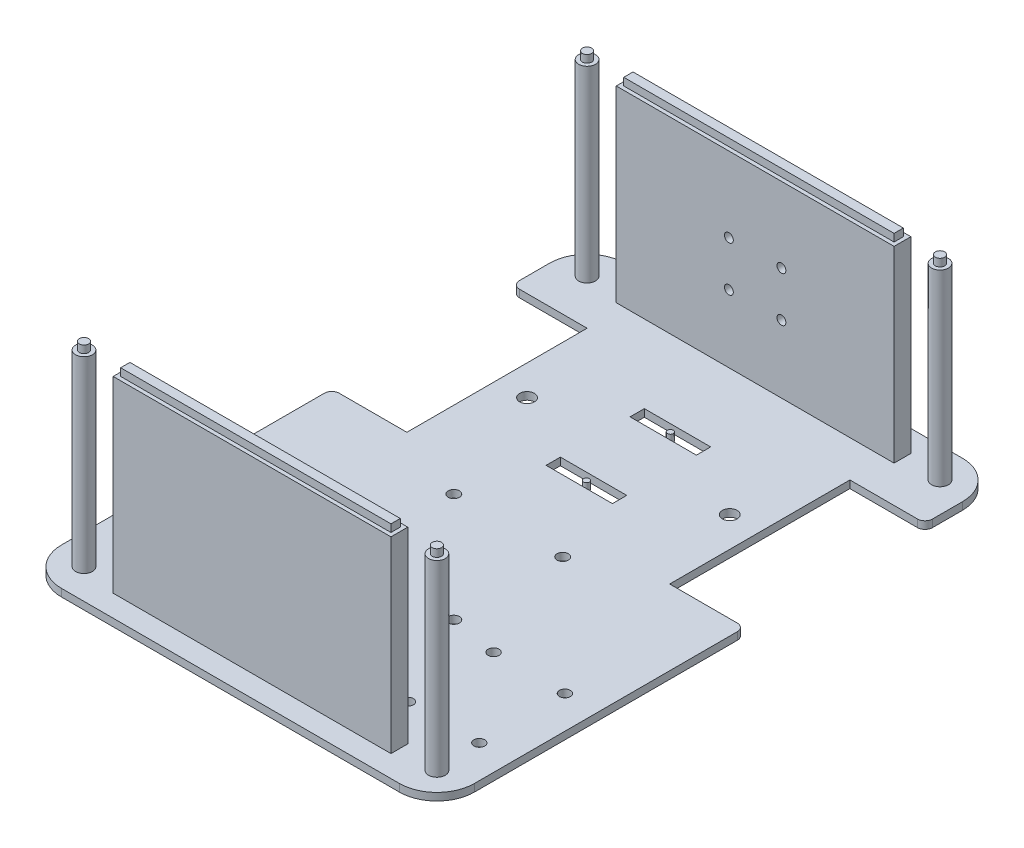
SolidWorks part; units mm, degrees
material "ABS"
ref_plane "Front Plane" through (0, 0, 0) normal (0, 0, 1) x (1, 0, 0)
ref_plane "Top Plane" through (0, 0, 0) normal (0, 1, 0) x (1, 0, 0)
ref_plane "Right Plane" through (0, 0, 0) normal (1, 0, 0) x (0, 0, -1)
sketch "Sketch2" plane through (0, 0, 0) normal (0, 1, 0) x (1, 0, 0)
  line L0 (-148.7583, 0) -> (98.0966, 0) construction
  line L1 (-69.85, -95.25) -> (69.85, -95.25)
  line L2 (-69.85, -95.25) -> (-69.85, 95.25)
  line L3 (-69.85, 95.25) -> (69.85, 95.25)
  line L4 (69.85, -95.25) -> (69.85, 95.25)
  line L5 (-69.85, -95.25) -> (69.85, 95.25) construction
  line L6 (-69.85, 95.25) -> (69.85, -95.25) construction
  line L7 (0, 121.1686) -> (0, -125.6862) construction
  point P0 (0, 0)
  dimension "D1" = 190.5
  dimension "D2" = 139.7
extrude "Base Plate" add sketch "Sketch2" along normal blind 2.54
sketch "Sketch4" plane through (0, 2.54, 0) normal (0, 1, 0) x (1, 0, 0)
  line L0 (0, -95.25) -> (0, 95.25) construction
  line L1 (-69.85, -95.25) -> (69.85, -95.25) construction
  line L2 (69.85, 95.25) -> (-69.85, 95.25) construction
  line L3 (-34.66, -69.85) -> (-34.66, -40.894) construction
  line L4 (-34.66, -40.894) -> (-58.79, -40.894) construction
  line L5 (-58.79, -40.894) -> (-58.79, -69.85) construction
  line L6 (-58.79, -69.85) -> (-34.66, -69.85) construction
  line L7 (69.85, -95.25) -> (69.85, 95.25) construction
  line L8 (-69.85, 95.25) -> (-69.85, -95.25) construction
  circle A0 centre (-58.79, -69.85) radius 1.8415
  circle A1 centre (-34.66, -69.85) radius 1.8415
  circle A2 centre (-34.66, -40.894) radius 1.8415
  circle A3 centre (-58.79, -40.894) radius 1.8415
  circle A4 centre (34.66, -69.85) radius 1.8415
  circle A5 centre (58.79, -69.85) radius 1.8415
  circle A6 centre (58.79, -40.894) radius 1.8415
  circle A7 centre (34.66, -40.894) radius 1.8415
  point P0 (-58.79, -69.85)
  point P1 (-58.79, -40.894)
  point P2 (-34.66, -40.894)
  point P3 (-34.66, -69.85)
  dimension "D4" = 3.683
  dimension "D1" = 28.956
  dimension "D2" = 24.13
  dimension "D3" = 11.06
  dimension "D5" = 25.4
extrude "L-Bracket holes" cut sketch "Sketch4" against normal blind 6.35
sketch "Sketch5" plane through (0, 2.54, 0) normal (0, 1, 0) x (1, 0, 0)
  line L0 (-69.85, 8.89) -> (-44.45, 8.89)
  line L1 (-69.85, 95.25) -> (-69.85, -95.25) construction
  line L2 (-44.45, 8.89) -> (-44.45, 69.85)
  line L3 (-44.45, 69.85) -> (-69.85, 69.85)
  line L4 (-69.85, 69.85) -> (-69.85, 8.89)
  line L5 (-69.85, -95.25) -> (69.85, -95.25) construction
  line L6 (69.85, 95.25) -> (-69.85, 95.25) construction
  line L7 (0, -95.25) -> (0, 95.25) construction
  line L8 (-58.79, -40.894) -> (-34.66, -40.894) construction
  line L9 (44.45, 69.85) -> (69.85, 69.85)
  line L10 (44.45, 8.89) -> (44.45, 69.85)
  line L11 (69.85, 8.89) -> (44.45, 8.89)
  line L12 (69.85, 69.85) -> (69.85, 8.89)
  dimension "D1" = 25.4
  dimension "D2" = 60.96
  dimension "D3" = 25.4
extrude "Steering Wheels Holes" cut sketch "Sketch5" against normal blind 6.35
fillet "Fillet1" radius 12.7 4 edges at (69.85, 1.27, -95.25) (-69.85, 1.27, -95.25) (69.85, 1.27, 95.25) (-69.85, 1.27, 95.25)
fillet "Fillet2" radius 2.54 4 edges at (69.85, 1.27, -69.85) (69.85, 1.27, -8.89) (-69.85, 1.27, -8.89) (-69.85, 1.27, -69.85)
sketch "Sketch6" plane through (0, 2.54, 0) normal (0, 1, 0) x (1, 0, 0)
  line L0 (-69.85, -95.25) -> (-69.85, 95.25) construction
  line L1 (-69.85, -95.25) -> (69.85, -95.25) construction
  line L2 (0, -88.935) -> (0, 95.5267) construction
  line L3 (-69.85, 6.35) -> (69.85, 6.35) construction
  point P0 (-59.69, -85.09)
  point P12 (-59.69, 97.79)
  point P13 (59.69, -85.09)
  point P14 (59.69, 97.79)
  dimension "D1" = 10.16
  dimension "D2" = 10.16
sketch "Sketch13" plane through (0, 2.54, 0) normal (0, 1, 0) x (1, 0, 0)
  line L0 (-69.85, -38.1) -> (69.85, -38.1) construction
  line L2 (-69.85, 6.35) -> (-69.85, -82.55) construction
  line L3 (69.85, -82.55) -> (69.85, 6.35) construction
  line L5 (-34.66, -69.85) -> (-34.66, -40.894) construction
  line L6 (34.66, -69.85) -> (34.66, -40.894) construction
  line L7 (-18.415, -38.1) -> (18.415, -38.1) construction
  line L8 (18.415, -38.1) -> (18.415, -1.27) construction
  line L9 (18.415, -1.27) -> (-18.415, -1.27) construction
  line L10 (-18.415, -1.27) -> (-18.415, -38.1) construction
  circle A0 centre (-18.415, -1.27) radius 1.905
  circle A1 centre (-18.415, -38.1) radius 1.905
  circle A2 centre (18.415, -38.1) radius 1.905
  circle A3 centre (18.415, -1.27) radius 1.905
  dimension "D1" = 3.81
  dimension "D4" = 36.83
  dimension "D5" = 36.83
extrude "Holes for L298" cut sketch "Sketch13" against normal blind 6.35
sketch "Sketch14" plane through (0, 2.54, 0) normal (0, 1, 0) x (1, 0, 0)
  line L0 (11.2203, 51.155) -> (-11.2203, 51.155)
  line L1 (11.2203, 22.755) -> (-11.2203, 22.755)
  line L2 (11.2203, 22.755) -> (11.2203, 27.585)
  line L3 (11.2203, 27.585) -> (-11.2203, 27.585)
  line L4 (0, 95.25) -> (0, -56.8347) construction
  line L5 (57.15, 95.25) -> (-57.15, 95.25) construction
  line L6 (-11.2203, 22.755) -> (-11.2203, 27.585)
  line L7 (-44.45, 39.37) -> (44.45, 39.37) construction
  line L8 (-44.45, 8.89) -> (-44.45, 69.85) construction
  line L9 (44.45, 69.85) -> (44.45, 8.89) construction
  line L10 (11.2203, 22.755) -> (-11.2203, 27.585) construction
  line L11 (11.2203, 27.585) -> (-11.2203, 22.755) construction
  line L12 (-11.2203, 55.985) -> (-11.2203, 51.155)
  line L13 (11.2203, 55.985) -> (-11.2203, 55.985)
  line L14 (11.2203, 55.985) -> (11.2203, 51.155)
  circle A2 centre (0, 25.17) radius 0.9906
  circle A3 centre (0, 53.57) radius 0.9906
  dimension "D3" = 4.83
  dimension "D2" = 1.9812
  dimension "D1" = 14.2
extrude "Cut-Extrude4" cut sketch "Sketch14" against normal blind 6.35
sketch "Sketch15" plane through (0, 2.54, 0) normal (0, 1, 0) x (1, 0, 0)
  line L0 (-69.85, -95.25) -> (-69.85, 95.25) construction
  line L1 (-69.85, 95.25) -> (69.85, 95.25) construction
  line L2 (0, 95.25) -> (0, 49.0943) construction
  line L3 (0, 121.1686) -> (0, -125.6862) construction
  circle A0 centre (-59.69, 85.09) radius 1.57
  circle A1 centre (-59.69, 85.09) radius 2.84
  point P0 (-59.69, 85.09)
  point P5 (59.69, 85.09)
  dimension "D3" = 3.14
  dimension "D1" = 10.16
  dimension "D2" = 10.16
  dimension "D4" = 1.27
sketch "Sketch18" plane through (0, 2.54, 0) normal (0, 1, 0) x (1, 0, 0)
  line L0 (-44.45, 39.37) -> (44.45, 39.37) construction
  line L1 (-44.45, 8.89) -> (-44.45, 69.85) construction
  line L2 (44.45, 69.85) -> (44.45, 8.89) construction
  line L3 (0, 95.25) -> (0, -95.25) construction
  line L4 (57.15, 95.25) -> (-57.15, 95.25) construction
  line L5 (-57.15, -95.25) -> (57.15, -95.25) construction
  point P12 (-34.29, 39.37)
  point P13 (34.29, 39.37)
  dimension "D1" = 10.16
hole_wizard "holes for steering" positions "Sketch19" profile "Sketch20" tap size "M6x1.0" standard "ANSI Metric" end condition through all
sketch "Sketch19" plane through (0, 2.54, 0) normal (0, 1, 0) x (1, 0, 0)
  point P0 (-34.29, 39.37)
  point P3 (34.29, 39.37)
sketch "Sketch20" plane through (-34.29, 2.54, -39.37) normal (1, 0, 0) x (0, 0, 1)
  line L0 (0, 0) -> (0, 2.54)
  line L1 (0, 2.54) -> (2.5, 2.54)
  line L2 (2.5, 2.54) -> (2.5, 0)
  line L5 (2.5, 0) -> (0, 0)
  line L11 (0, -6.35) -> (0, 107.95) construction
  dimension "Thru Tap Drill Dia." = 5
  dimension "Thru Tap Drill Depth" = 2.54
cosmetic thread "Hole Thread11" parameters "D2"=6
cosmetic thread "Hole Thread12" parameters "D2"=6
extrude "Boss-Extrude3" add sketch "Sketch15" along normal blind 63.5
extrude "Boss-Extrude4" add sketch "Sketch15<2>" along normal blind 66.04 contours A0 region at (-59.69, 2.54, -85.09)
sketch "Sketch15<2>" plane through (0, 2.54, 0) normal (0, 1, 0) x (1, 0, 0) same geometry as "Sketch15"
mirror "Mirror1" about plane through (0, 0, 0) normal (1, 0, 0) of "Boss-Extrude4"
mirror "Mirror2" about plane through (0, 0, 0) normal (1, 0, 0) of "Boss-Extrude3"
sketch "Sketch23" plane through (0, 2.54, 0) normal (0, 1, 0) x (1, 0, 0)
  line L0 (0, 95.25) -> (0, -95.25) construction
  line L1 (-69.85, 6.35) -> (-69.85, -82.55) construction
  line L2 (-57.15, -95.25) -> (57.15, -95.25) construction
  circle A0 centre (-59.69, -85.09) radius 1.57
  circle A1 centre (-59.69, -85.09) radius 2.84
  dimension "D1" = 3.14
  dimension "D3" = 10.16
  dimension "D4" = 10.16
  dimension "D2" = 1.27
extrude "Boss-Extrude5" add sketch "Sketch23" along normal blind 63.5
extrude "Boss-Extrude6" add sketch "Sketch23<2>" along normal blind 66.04 contours A0 region at (-59.69, 2.54, 85.09)
sketch "Sketch23<2>" plane through (0, 2.54, 0) normal (0, 1, 0) x (1, 0, 0) same geometry as "Sketch23"
mirror "Mirror3" about plane through (0, 0, 0) normal (1, 0, 0) of "Boss-Extrude6", "Boss-Extrude5"
sketch "Sketch24" plane through (0, 2.54, 0) normal (0, 1, 0) x (1, 0, 0)
  line L0 (-59.69, -87.93) -> (59.69, -87.93) construction
  line L1 (-59.69, -82.25) -> (59.69, -82.25) construction
  line L2 (-59.69, 82.25) -> (59.69, 82.25) construction
  line L3 (-46.99, -87.93) -> (46.99, -87.93)
  line L4 (-46.99, -87.93) -> (-46.99, -82.25)
  line L5 (-46.99, -82.25) -> (46.99, -82.25)
  line L6 (46.99, -87.93) -> (46.99, -82.25)
  line L7 (59.69, 87.93) -> (-59.69, 87.93) construction
  line L9 (-46.99, 82.25) -> (46.99, 82.25)
  line L10 (-46.99, 82.25) -> (-46.99, 87.93)
  line L11 (-46.99, 87.93) -> (46.99, 87.93)
  line L12 (46.99, 82.25) -> (46.99, 87.93)
  circle A0 centre (-59.69, -85.09) radius 2.84 construction
  circle A1 centre (59.69, -85.09) radius 2.84 construction
  circle A2 centre (-59.69, -85.09) radius 2.84 construction
  circle A3 centre (-59.69, 85.09) radius 2.84 construction
  circle A4 centre (-59.69, 85.09) radius 2.84 construction
  circle A5 centre (59.69, 85.09) radius 2.84 construction
  circle A6 centre (59.69, 85.09) radius 2.84 construction
  dimension "D1" = 12.7
  dimension "D2" = 12.7
  dimension "D3" = 12.7
  dimension "D4" = 12.7
extrude "Boss-Extrude7" add sketch "Sketch24" along normal blind 63.5
sketch "Sketch25" plane through (0, 66.04, 0) normal (0, 1, 0) x (1, 0, 0)
  line L8 (-45.72, -83.52) -> (-45.72, -86.66)
  line L9 (-45.72, -86.66) -> (45.72, -86.66)
  line L10 (45.72, -86.66) -> (45.72, -83.52)
  line L11 (45.72, -83.52) -> (-45.72, -83.52)
  line L12 (-45.72, -83.52) -> (-45.72, -86.66)
  line L13 (-45.72, -86.66) -> (45.72, -86.66)
  line L14 (45.72, -86.66) -> (45.72, -83.52)
  line L15 (45.72, -83.52) -> (-45.72, -83.52)
  line L20 (-45.72, 86.66) -> (-45.72, 83.52)
  line L21 (-45.72, 83.52) -> (45.72, 83.52)
  line L22 (45.72, 83.52) -> (45.72, 86.66)
  line L23 (45.72, 86.66) -> (-45.72, 86.66)
  line L24 (-45.72, 86.66) -> (-45.72, 83.52)
  line L25 (-45.72, 83.52) -> (45.72, 83.52)
  line L26 (45.72, 83.52) -> (45.72, 86.66)
  line L27 (45.72, 86.66) -> (-45.72, 86.66)
  dimension "D1" = 1.27
  dimension "D2" = 1.27
extrude "Boss-Extrude8" add sketch "Sketch25" along normal blind 2.54
sketch "Sketch26" plane through (0, 0, -87.93) normal (0, 0, -1) x (-1, 0, 0)
  line L0 (0, 66.04) -> (0, 83.3576) construction
  line L1 (-46.99, 66.04) -> (46.99, 66.04) construction
  line L2 (-8.89, 40.64) -> (-8.89, -18.1923) construction
  circle A0 centre (-8.89, 40.64) radius 1.5
  circle A1 centre (-8.89, 25.4) radius 1.5
  circle A2 centre (8.89, 25.4) radius 1.5
  circle A3 centre (8.89, 40.64) radius 1.5
  dimension "D1" = 3
  dimension "D3" = 3
  dimension "D2" = 8.89
  dimension "D4" = 15.24
  dimension "D5" = 25.4
extrude "Cut-Extrude5" cut sketch "Sketch26" against normal up to next (5.68 mm away)
